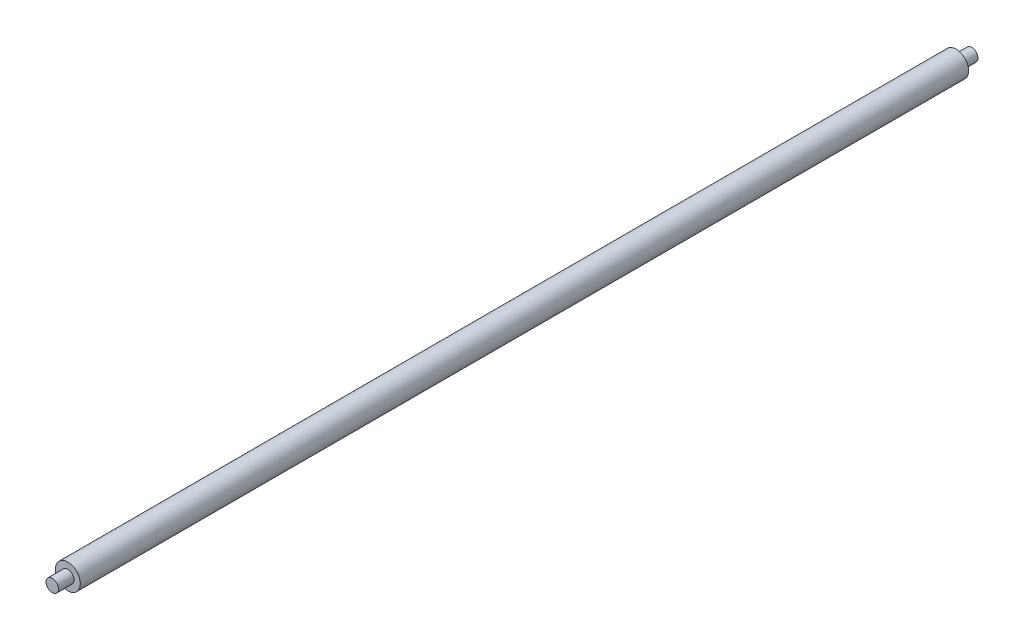
SolidWorks part; units mm, degrees
ref_plane "Front Plane" through (0, 0, 0) normal (0, 0, 1) x (1, 0, 0)
ref_plane "Top Plane" through (0, 0, 0) normal (0, 1, 0) x (1, 0, 0)
ref_plane "Right Plane" through (0, 0, 0) normal (1, 0, 0) x (0, 0, -1)
sketch "Sketch1" plane through (0, 0, 0) normal (0, 0, 1) x (1, 0, 0)
  circle A0 centre (0, 0) radius 6
  dimension "D1" = 12
extrude "Boss-Extrude1" add sketch "Sketch1" along normal mid plane 427.5
sketch "Sketch2" plane through (0, 0, 213.75) normal (0, 0, 1) x (1, 0, 0)
  circle A1 centre (0, 0) radius 3
  dimension "D2" = 6
sketch "Sketch3" plane through (0, 0, -213.75) normal (0, 0, -1) x (-1, 0, 0)
  circle A1 centre (0, 0) radius 3
  dimension "D1" = 6
extrude "Boss-Extrude4" add sketch "Sketch2" along normal blind 7.5
extrude "Boss-Extrude5" add sketch "Sketch3" along normal blind 7.5
